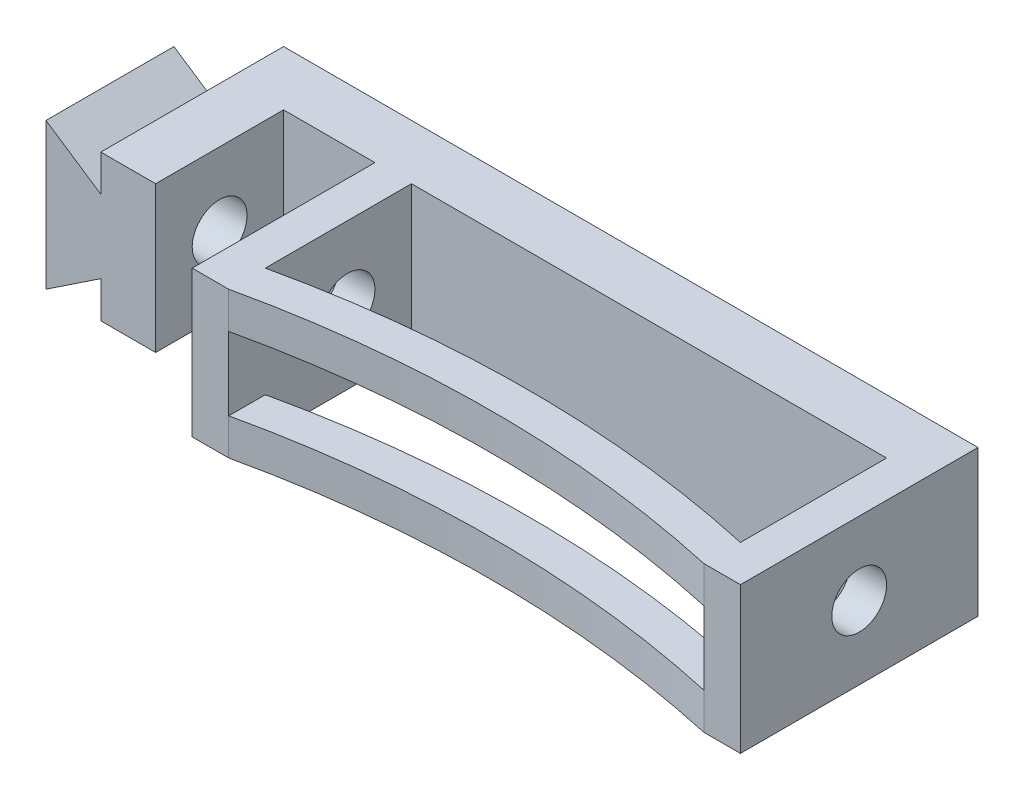
SolidWorks part; units mm, degrees
ref_plane "前视基准面" through (0, 0, 0) normal (0, 0, 1) x (1, 0, 0)
ref_plane "上视基准面" through (0, 0, 0) normal (0, 1, 0) x (1, 0, 0)
ref_plane "右视基准面" through (0, 0, 0) normal (1, 0, 0) x (0, 0, -1)
sketch "草图1" plane through (0, 0, 0) normal (0, 0, 1) x (1, 0, 0)
  line L1 (-3, 6) -> (-3, -2)
  line L2 (0, 2) -> (-10.3321, 2) construction
  line L3 (-3, 6) -> (0, 4)
  line L4 (-3, -2) -> (0, 0)
  line L5 (0, 0) -> (0, -2)
  line L6 (0, 6) -> (3, 6)
  line L7 (0, 6) -> (0, 4)
  line L8 (0, -2) -> (3, -2)
  line L9 (3, 6) -> (3, -2)
  line L10 (0, 4) -> (0, 0)
  line L11 (3, 6) -> (38, 6)
  line L12 (3, 6) -> (3, -2)
  line L13 (3, -2) -> (38, -2)
  line L14 (38, 6) -> (38, -2)
  point P7 (-3, 2)
  dimension "D1" = 4
  dimension "D2" = 8
  dimension "D3" = 35
  dimension "D4" = 3
  dimension "D5" = 8
  dimension "D6" = 3
extrude "凸台-拉伸2" add sketch "草图1" along normal blind 10 contours L2 L10 L3 L1 | L7 L10 L5 L8 L9 L6 | L10 L2 L1 L4 | L14 L11 L9 L13 region at (-1.6667, 3.5556, 0) region at (-1.6667, 0.4444, 0) region at (1.5, 2, 0) region at (20.5, 2, 0)
extrude "切除-拉伸4" cut sketch "草图1<4>" along normal blind 3 contours L2 L10 L3 L1 | L10 L2 L1 L4 region at (-1.6667, 3.5556, 0) region at (-1.6667, 0.4444, 0)
sketch "草图1<4>" plane through (0, 0, 0) normal (0, 0, 1) x (1, 0, 0) same geometry as "草图1"
sketch "草图11" plane through (0, 0, 10) normal (0, 0, 1) x (1, 0, 0)
  line L0 (0, -2) -> (38, -2) construction
  line L1 (38, 6) -> (3, 6)
  line L2 (38, 6) -> (38, -2)
  line L3 (38, -2) -> (3, -2)
  line L4 (3, 6) -> (3, -2)
  line L5 (0, 6) -> (0, 4) construction
  dimension "D1" = 3
extrude "切除-拉伸5" cut sketch "草图11" against normal offset from surface (7 mm away) 3 up to face at (19, 2, 0)
sketch "草图14" plane through (0, 0, 3) normal (0, 0, 1) x (1, 0, 0)
  line L0 (38, -2) -> (3, -2) construction
  line L1 (38, 6) -> (36, 6)
  line L2 (38, 6) -> (38, -2)
  line L3 (38, -2) -> (36, -2)
  line L4 (36, 6) -> (36, -2)
  line L5 (3, 6) -> (38, 6) construction
  line L6 (8, 6) -> (10, 6)
  line L7 (8, 6) -> (8, -2)
  line L8 (8, -2) -> (10, -2)
  line L9 (10, 6) -> (10, -2)
  line L10 (3, 6) -> (3, -2) construction
  dimension "D1" = 2
  dimension "D2" = 2
  dimension "D3" = 5
extrude "凸台-拉伸7" add sketch "草图14" along normal blind 10
sketch "草图12" plane through (3, 0, 0) normal (1, 0, 0) x (0, 0, -1)
  line L0 (-10, 2) -> (-3, 2) construction
  line L1 (-10, 6) -> (-10, -2) construction
  line L2 (-3, -2) -> (-3, 6) construction
  line L3 (-6.5, 6) -> (-6.5, -2) construction
  line L4 (-3, 6) -> (-10, 6) construction
  line L5 (-3, -2) -> (-10, -2) construction
  circle A0 centre (-6.5, 2) radius 1.5
  dimension "D1" = 3
extrude "切除-拉伸6" cut sketch "草图12" against normal blind 3 and the other way through all
sketch "草图30" plane through (0, 6, 0) normal (0, 1, 0) x (1, 0, 0)
  line L1 (10, -13) -> (10, -3) construction
  line L2 (36, -13) -> (36, -3) construction
  line L3 (10, -11) -> (36, -11) construction
  line L4 (10, -11) -> (10, -13)
  line L5 (36, -11) -> (36, -13)
  arc A0 (10, -13) -> (36, -13) centre (23, -71.5747) cw
  arc A1 (10, -11) -> (36, -11) centre (23, -69.5747) cw
  dimension "D1" = 60
  dimension "D2" = 60
  dimension "D3" = 2
extrude "凸台-拉伸10" add sketch "草图30" against normal blind 8
sketch "草图31" plane through (0, 0, 13) normal (0, 0, 1) x (1, 0, 0)
  line L0 (8, 2) -> (3, 2) construction
  line L1 (8, 6) -> (8, -2) construction
  line L2 (3, 6) -> (3, -2) construction
  line L3 (10, -2) -> (10, 6) construction
  line L4 (10, 4) -> (36, 4)
  line L5 (10, 4) -> (10, 0)
  line L6 (10, 0) -> (36, 0)
  line L7 (36, 4) -> (36, 0)
  line L8 (36, 6) -> (36, -2) construction
  dimension "D1" = 4
extrude "切除-拉伸8" cut sketch "草图31" against normal up to next and the other way through all
